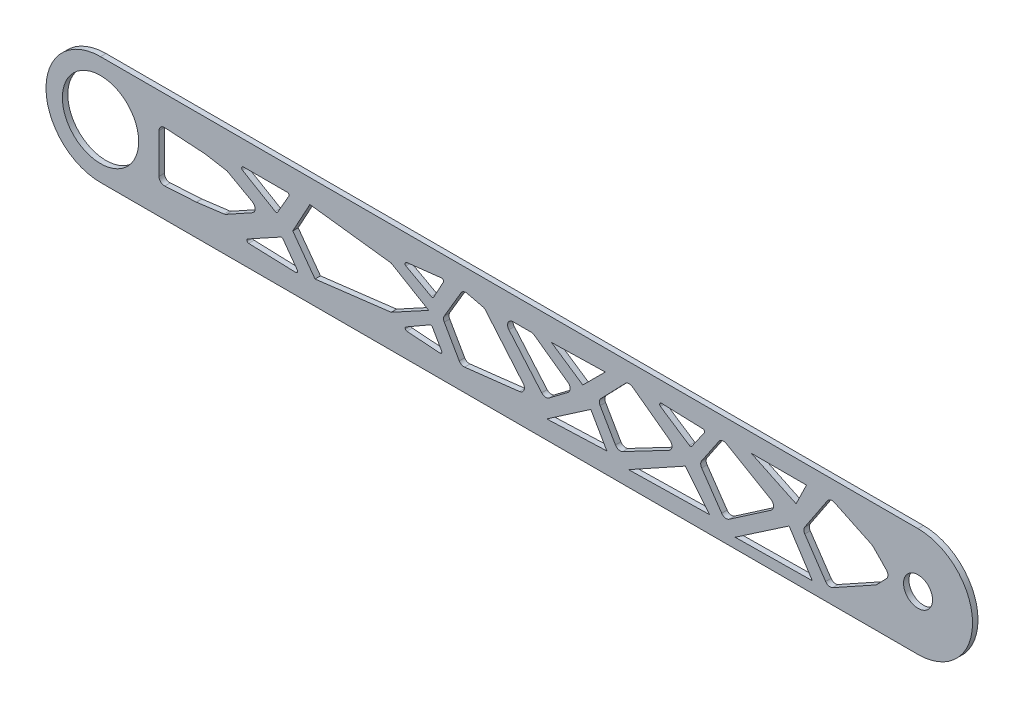
SolidWorks part; units mm, degrees
material "6061-T6 (SS)"
ref_plane "Front Plane" through (0, 0, 0) normal (0, 0, 1) x (1, 0, 0)
ref_plane "Top Plane" through (0, 0, 0) normal (0, 1, 0) x (1, 0, 0)
ref_plane "Right Plane" through (0, 0, 0) normal (1, 0, 0) x (0, 0, -1)
sketch "Sketch1" plane through (0, 0, 0) normal (0, 0, 1) x (1, 0, 0)
  line L0 (0, 0) -> (450, 0) construction
  line L1 (0, 30) -> (450, 30)
  line L2 (0, -30) -> (450, -30)
  arc A0 (0, 30) -> (0, -30) centre (0, 0) ccw
  arc A1 (450, -30) -> (450, 30) centre (450, 0) ccw
  circle A2 centre (0, 0) radius 21
  circle A9 centre (0, 0) radius 10 construction
  point P3 (225, 0)
  point P24 (0, 0)
  dimension "D1" = 30
  dimension "D3" = 42
  dimension "D6" = 20
  dimension "D2" = 450
extrude "Boss-Extrude1" add sketch "Sketch1" along normal blind 3
sketch "Sketch2" plane through (0, 0, 0) normal (0, 0, -1) x (-1, 0, 0)
  circle A0 centre (-450, 0) radius 8
  dimension "D1" = 16
extrude "Cut-Extrude1" cut sketch "Sketch2" against normal blind 10
sketch "Sketch3" plane through (0, 0, 0) normal (0, 0, -1) x (-1, 0, 0)
  line L0 (-225, 30) -> (-225, -30) construction
  line L1 (-450, 30) -> (0, 30) construction
  line L2 (0, -30) -> (-450, -30) construction
sketch "Sketch4" plane through (0, 0, 3) normal (0, 0, 1) x (1, 0, 0)
  line L3 (75.0512, 16.7519) -> (104.4964, 16.7519)
  line L4 (104.4964, 16.7519) -> (97.0103, 3.776)
  line L5 (97.0103, 3.776) -> (75.0512, 16.7519)
  line L6 (115.2364, 17.1336) -> (159.9949, 11.5901)
  line L7 (159.9949, 11.5901) -> (180.6552, -0.6182)
  line L8 (159.9949, -11.858) -> (118.0851, -16.9668)
  line L9 (118.0851, -16.9668) -> (105.8233, -0.1776)
  line L10 (105.8233, -0.1776) -> (115.2364, 17.1336)
  line L11 (189.6655, 18.5783) -> (182.9411, 6.2118)
  line L12 (189.6655, 18.5783) -> (165.3685, 15.767)
  line L13 (165.3685, 15.767) -> (182.9411, 6.2118)
  line L14 (199.5998, 18.5783) -> (188.3613, -0.4406)
  line L15 (188.3613, -0.4406) -> (198.4445, -18.0218)
  line L16 (198.4445, -18.0218) -> (236.2169, -13.6513)
  line L17 (236.2169, -13.6513) -> (211.3582, 15.767)
  line L18 (211.3582, 15.767) -> (199.5998, 18.5783)
  line L19 (220.5269, 17.1727) -> (237.9604, 17.1727)
  line L20 (237.9604, 17.1727) -> (260.5594, 1.0579)
  line L21 (244.6755, -10.9439) -> (220.5269, 17.1727)
  line L22 (265.4666, 6.2118) -> (277.8331, 18.5783)
  line L23 (277.8331, 18.5783) -> (248.2204, 17.8749)
  line L24 (248.2204, 17.8749) -> (265.4666, 6.2118)
  line L25 (165.3685, -16.3587) -> (182.2005, -6.7053)
  line L26 (182.2005, -6.7053) -> (188.6908, -18.0218)
  line L27 (188.6908, -18.0218) -> (165.3685, -16.3587)
  line L28 (245.6374, -19.8683) -> (269.8878, -3.2204)
  line L29 (269.8878, -3.2204) -> (278.7166, -18.6146)
  line L30 (278.7166, -18.6146) -> (245.6374, -19.8683)
  line L32 (290.6832, -21.5398) -> (321.9406, -4.2114)
  line L33 (321.9406, -4.2114) -> (335.2064, -20.704)
  line L34 (335.2064, -20.704) -> (290.6832, -21.5398)
  line L35 (341.9929, 19.1834) -> (329.7352, 1.0579)
  line L36 (329.7352, 1.0579) -> (343.6146, -19.1598)
  line L37 (343.6146, -19.1598) -> (373.065, 1.0579)
  line L38 (373.065, 1.0579) -> (341.9929, 19.1834)
  line L39 (244.6755, -10.9439) -> (260.5594, 1.0579)
  line L40 (273.8778, 3.1142) -> (290.6832, 20.5427)
  line L41 (290.6832, 20.5427) -> (317.2099, 1.0579)
  line L42 (317.2099, 1.0579) -> (284.8817, -15.8863)
  line L43 (284.8817, -15.8863) -> (273.8778, 3.1142)
  line L44 (305.3074, 19.271) -> (333.3759, 18.3243)
  line L45 (333.3759, 18.3243) -> (324.9421, 6.2118)
  line L46 (324.9421, 6.2118) -> (305.3074, 19.271)
  line L47 (358.198, 20.0502) -> (388.5975, 20.0502)
  line L48 (388.5975, 20.0502) -> (382.8865, 8.2928)
  line L49 (382.8865, 8.2928) -> (358.198, 20.0502)
  line L50 (349.331, -24.4281) -> (379.0302, -4.2114)
  line L51 (379.0302, -4.2114) -> (391.83, -23.927)
  line L52 (391.83, -23.927) -> (349.331, -24.4281)
  line L53 (386.543, -2.0485) -> (401.5864, 20.5696)
  line L54 (401.5864, 20.5696) -> (424.8813, 9.4759)
  line L55 (434.601, -0.4406) -> (424.8813, 9.4759)
  line L56 (434.601, -0.4406) -> (426.9833, -8.3408)
  line L57 (426.9833, -8.3408) -> (400.6645, -22.9126)
  line L58 (400.6645, -22.9126) -> (386.543, -2.0485)
  line L59 (159.9949, -11.858) -> (180.6552, -0.6182)
  line L60 (77.9082, -18.1131) -> (99.9591, -5.986)
  line L61 (99.9591, -5.986) -> (109.5177, -19.2166)
  line L62 (109.5177, -19.2166) -> (77.9082, -18.1131)
  line L63 (32.1814, 14.0452) -> (32.1814, -14.1865)
  line L64 (32.1814, -14.1865) -> (52.8225, -12.9556)
  line L65 (52.8225, -12.9556) -> (68.5544, -10.9439)
  line L66 (68.5544, -10.9439) -> (88.303, 0)
  line L67 (88.303, 0) -> (69.6625, 10.3469)
  line L68 (69.6625, 10.3469) -> (57.5717, 12.4236)
  line L69 (57.5717, 12.4236) -> (32.1814, 14.0452)
extrude "Cut-Extrude2" cut sketch "Sketch4" against normal blind 10
fillet "Fillet1" radius 3 7 edges at (57.5717, 12.4236, 1.5) (69.6625, 10.3469, 1.5) (88.303, 0, 1.5) (52.8225, -12.9556, 1.5) (68.5544, -10.9439, 1.5) (32.1814, -14.1865, 1.5) (32.1814, 14.0452, 1.5)
fillet "Fillet2" radius 1 15 edges at (324.9421, 6.2118, 1.5) (333.3759, 18.3243, 1.5) (305.3074, 19.271, 1.5) (189.6655, 18.5783, 1.5) (182.9411, 6.2118, 1.5) (165.3685, 15.767, 1.5) (182.2005, -6.7053, 1.5) (188.6908, -18.0218, 1.5) (165.3685, -16.3587, 1.5) (109.5177, -19.2166, 1.5) (99.9591, -5.986, 1.5) (77.9082, -18.1131, 1.5) (97.0103, 3.776, 1.5) (104.4964, 16.7519, 1.5) (75.0512, 16.7519, 1.5)
fillet "Fillet3" radius 3 23 edges at (400.6645, -22.9126, 1.5) (401.5864, 20.5696, 1.5) (260.5594, 1.0579, 1.5) (220.5269, 17.1727, 1.5) (244.6755, -10.9439, 1.5) (343.6146, -19.1598, 1.5) (284.8817, -15.8863, 1.5) (317.2099, 1.0579, 1.5) (236.2169, -13.6513, 1.5) (237.9604, 17.1727, 1.5) (211.3582, 15.767, 1.5) (199.5998, 18.5783, 1.5) (341.9929, 19.1834, 1.5) (290.6832, 20.5427, 1.5) (198.4445, -18.0218, 1.5) (188.3613, -0.4406, 1.5) (273.8778, 3.1142, 1.5) (329.7352, 1.0579, 1.5) (386.543, -2.0485, 1.5) (424.8813, 9.4759, 1.5) (426.9833, -8.3408, 1.5) (434.601, -0.4406, 1.5) (373.065, 1.0579, 1.5)
